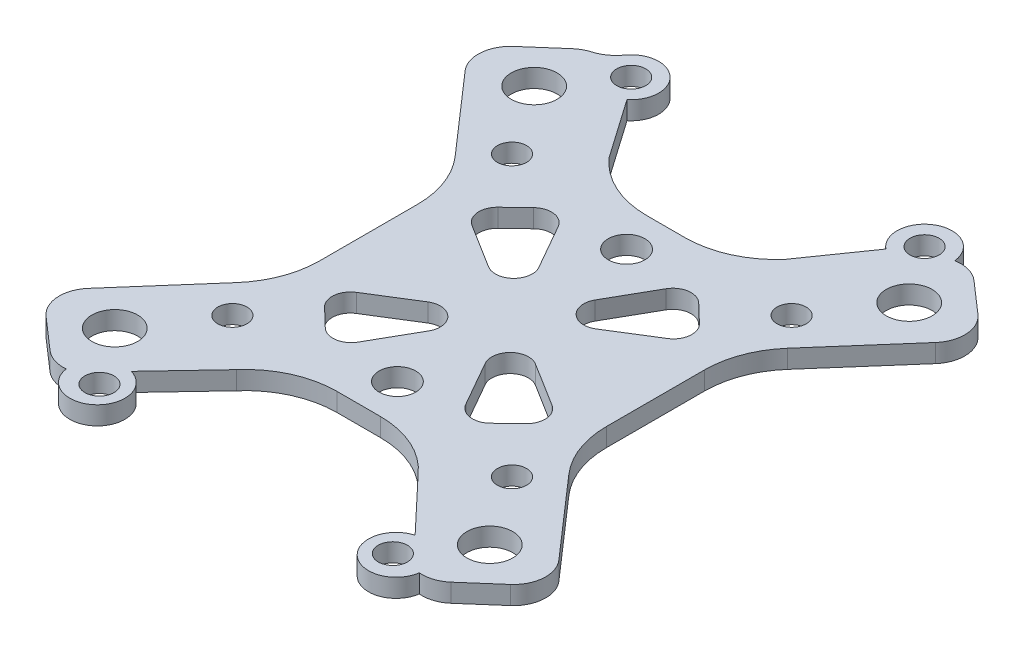
SolidWorks part; units mm, degrees
ref_plane "Alzado" through (0, 0, 0) normal (0, 0, 1) x (1, 0, 0)
ref_plane "Planta" through (0, 0, 0) normal (0, 1, 0) x (1, 0, 0)
ref_plane "Vista lateral" through (0, 0, 0) normal (1, 0, 0) x (0, 0, -1)
sketch "Croquis2" plane through (0, 0, 0) normal (0, 1, 0) x (1, 0, 0)
  line L0 (0, 0) -> (0, 10.4123) construction
  line L7 (-18.1147, -11.9133) -> (-25.6658, -20.5534)
  line L14 (-15.6443, 5.3327) -> (-15.6443, -5.3327)
  line L15 (-2.3687, -16.7202) -> (2.3687, -16.7202)
  line L16 (15.6443, 5.3327) -> (15.6443, -5.3327)
  line L17 (-13.8775, 14.4472) -> (-9.9975, 10.4079) construction
  line L18 (-2.0794, 16.7817) -> (2.0794, 16.7817)
  line L20 (-25.3337, -25.492) -> (-21.87, -28.5191)
  line L21 (18.1147, -11.9133) -> (25.6658, -20.5534)
  line L23 (25.3337, -25.492) -> (21.87, -28.5191)
  line L24 (25.3337, 25.492) -> (21.87, 28.5191)
  line L25 (9.6091, 20.2011) -> (14.1192, 26.6628)
  line L26 (18.1147, 11.9133) -> (25.6658, 20.5534)
  line L27 (-25.3337, 25.492) -> (-21.87, 28.5191)
  line L30 (-18.1147, 11.9133) -> (-25.6658, 20.5534)
  line L31 (-9.6091, 20.2011) -> (-14.1192, 26.6628)
  line L33 (9.8983, -20.1396) -> (15.4814, -26.0493)
  line L34 (-9.8983, -20.1396) -> (-15.4814, -26.0493)
  line L37 (0, 0) -> (-15.6443, 0) construction
  line L38 (-8.9971, 11.3688) -> (-10.9978, 9.447)
  line L39 (-10.671, 6.3078) -> (-5.8711, 3.3132)
  line L40 (-5.8736, 10.916) -> (-3.0744, 5.9996)
  line L41 (5.8736, 10.916) -> (3.0744, 5.9996)
  line L42 (10.671, 6.3078) -> (5.8711, 3.3132)
  line L43 (8.9971, 11.3688) -> (10.9978, 9.447)
  line L45 (8.9971, -11.3688) -> (10.9978, -9.447)
  line L46 (10.671, -6.3078) -> (5.8711, -3.3132)
  line L47 (5.8736, -10.916) -> (3.0744, -5.9996)
  line L48 (-5.8736, -10.916) -> (-3.0744, -5.9996)
  line L49 (-10.671, -6.3078) -> (-5.8711, -3.3132)
  line L50 (-8.9971, -11.3688) -> (-10.9978, -9.447)
  arc A19 (-19.2581, -29.3701) -> (-21.87, -28.5191) centre (-19.5668, -25.8837) cw
  arc A20 (-25.3337, -25.492) -> (-25.6658, -20.5534) centre (-23.0305, -22.8566) cw
  arc A21 (25.3337, -25.492) -> (25.6658, -20.5534) centre (23.0305, -22.8566) ccw
  arc A22 (19.2581, -29.3701) -> (21.87, -28.5191) centre (19.5668, -25.8837) ccw
  arc A23 (18.9829, 29.3199) -> (21.87, 28.5191) centre (19.581, 25.8714) cw
  arc A24 (25.3337, 25.492) -> (25.6658, 20.5534) centre (23.0305, 22.8566) cw
  arc A25 (-25.3337, 25.492) -> (-25.6658, 20.5534) centre (-23.0305, 22.8566) ccw
  arc A26 (-20.5688, 29.2291) -> (-21.87, 28.5191) centre (-19.581, 25.8714) ccw
  circle A43 centre (-16, 29) radius 1.5875
  arc A44 (-14.1192, 26.6628) -> (-18.4419, 30.7428) centre (-16, 29) ccw
  circle A45 centre (16, 29) radius 1.5875
  arc A48 (9.6091, 20.2011) -> (2.0794, 16.7817) centre (2.0794, 26.7817) cw
  arc A50 (-3.0744, 5.9996) -> (-5.8711, 3.3132) centre (-4.8125, 5.01) cw
  arc A51 (-8.9971, 11.3688) -> (-5.8736, 10.916) centre (-7.6116, 9.9264) cw
  arc A52 (-10.9978, 9.447) -> (-10.671, 6.3078) centre (-9.6123, 8.0046) ccw
  arc A53 (10.9978, 9.447) -> (10.671, 6.3078) centre (9.6123, 8.0046) cw
  arc A54 (8.9971, 11.3688) -> (5.8736, 10.916) centre (7.6116, 9.9264) ccw
  arc A55 (3.0744, 5.9996) -> (5.8711, 3.3132) centre (4.8125, 5.01) ccw
  arc A56 (8.9971, -11.3688) -> (5.8736, -10.916) centre (7.6116, -9.9264) cw
  arc A57 (-8.9971, -11.3688) -> (-5.8736, -10.916) centre (-7.6116, -9.9264) ccw
  arc A58 (3.0744, -5.9996) -> (5.8711, -3.3132) centre (4.8125, -5.01) cw
  arc A59 (10.9978, -9.447) -> (10.671, -6.3078) centre (9.6123, -8.0046) ccw
  arc A60 (-10.9978, -9.447) -> (-10.671, -6.3078) centre (-9.6123, -8.0046) cw
  arc A61 (-3.0744, -5.9996) -> (-5.8711, -3.3132) centre (-4.8125, -5.01) ccw
  circle A62 centre (0, 12.4971) radius 2
  circle A63 centre (0, -12.4971) radius 2
  arc A64 (-18.1147, 11.9133) -> (-15.6443, 5.3327) centre (-25.6443, 5.3327) cw
  arc A65 (-15.6443, -5.3327) -> (-18.1147, -11.9133) centre (-25.6443, -5.3327) cw
  arc A66 (-2.3687, -16.7202) -> (-9.8983, -20.1396) centre (-2.3687, -26.7202) ccw
  arc A67 (2.3687, -16.7202) -> (9.8983, -20.1396) centre (2.3687, -26.7202) cw
  arc A68 (15.6443, -5.3327) -> (18.1147, -11.9133) centre (25.6443, -5.3327) ccw
  arc A69 (18.1147, 11.9133) -> (15.6443, 5.3327) centre (25.6443, 5.3327) ccw
  arc A70 (14.1192, 26.6628) -> (18.9829, 29.3199) centre (16, 29) cw
  arc A71 (-9.6091, 20.2011) -> (-2.0794, 16.7817) centre (-2.0794, 26.7817) ccw
  arc A73 (15.4814, -26.0493) -> (19.2581, -29.3701) centre (16.2893, -28.9384) ccw
  circle A77 centre (-15.25, 15.25) radius 1.59
  arc A89 (-15.4814, -26.0493) -> (-19.2581, -29.3701) centre (-16.2893, -28.9384) cw
  circle A96 centre (-15.25, -15.25) radius 1.59
  circle A97 centre (-20.4532, 22.8733) radius 1.5974
  circle A98 centre (-20.4532, 22.8733) radius 2.5
  circle A99 centre (20.4532, 22.8733) radius 1.5974
  circle A100 centre (20.4532, 22.8733) radius 2.5
  circle A101 centre (20.4532, -22.8733) radius 1.5974
  circle A102 centre (20.4532, -22.8733) radius 2.5
  circle A103 centre (-20.4532, -22.8733) radius 1.5974
  circle A104 centre (-20.4532, -22.8733) radius 2.5
  arc A105 (-18.4419, 30.7428) -> (-20.5688, 29.2291) centre (-21.6977, 33.0665) cw
  circle A106 centre (15.25, -15.25) radius 1.59
  circle A107 centre (15.25, 15.25) radius 1.59
  circle A108 centre (-16, -29) radius 1.5875
  circle A109 centre (16, -29) radius 1.5875
  point P22 (-19.2347, -30.8223)
  point P25 (-27.9691, -23.1888)
  point P34 (27.9691, -23.1888)
  point P35 (19.2347, -30.8223)
  point P53 (19.2347, 30.8223)
  point P54 (-27.9691, 23.1888)
  point P55 (-19.2347, 30.8223)
  point P64 (-18.9829, 29.3199)
  point P89 (-9.9975, 10.4079)
  point P92 (0.8383, -0.8727)
  point P96 (-7.1445, 13.1483)
  point P99 (-12.8504, 7.6675)
  point P112 (12.8504, 7.6675)
  point P113 (7.1445, 13.1483)
  point P114 (9.9975, 10.4079)
  point P135 (9.9975, -10.4079)
  point P136 (12.8504, -7.6675)
  point P137 (-12.8504, -7.6675)
  point P138 (-9.9975, -10.4079)
  point P143 (-15.6443, 9.0867)
  point P146 (-15.6443, -9.0867)
  point P149 (-6.9099, -16.7202)
  point P152 (6.9099, -16.7202)
  point P155 (15.6443, -9.0867)
  point P158 (15.6443, 9.0867)
  dimension "D3" = 3.5
  dimension "D5" = 15.25
  dimension "D2" = 3.18
  dimension "D9" = 13.8199
  dimension "D10" = 3.175
  dimension "D12" = 10
  dimension "D13" = 6
  dimension "D8" = 2
  dimension "D11" = 4
  dimension "D4" = 5
  dimension "D6" = 4
  dimension "D14" = 15.25
  dimension "D15" = 16
  dimension "D16" = 29
extrude "Saliente-Extruir1" add sketch "Croquis2" along normal blind 2 contours L27 A100 A25 L30 A64 L14 A65 L7 A20 L20 A66 L15 A67 L23 A21 L21 A68 L16 A69 L26 A24 L24 A48 region at (-0.0067, 0, -0.3044)
